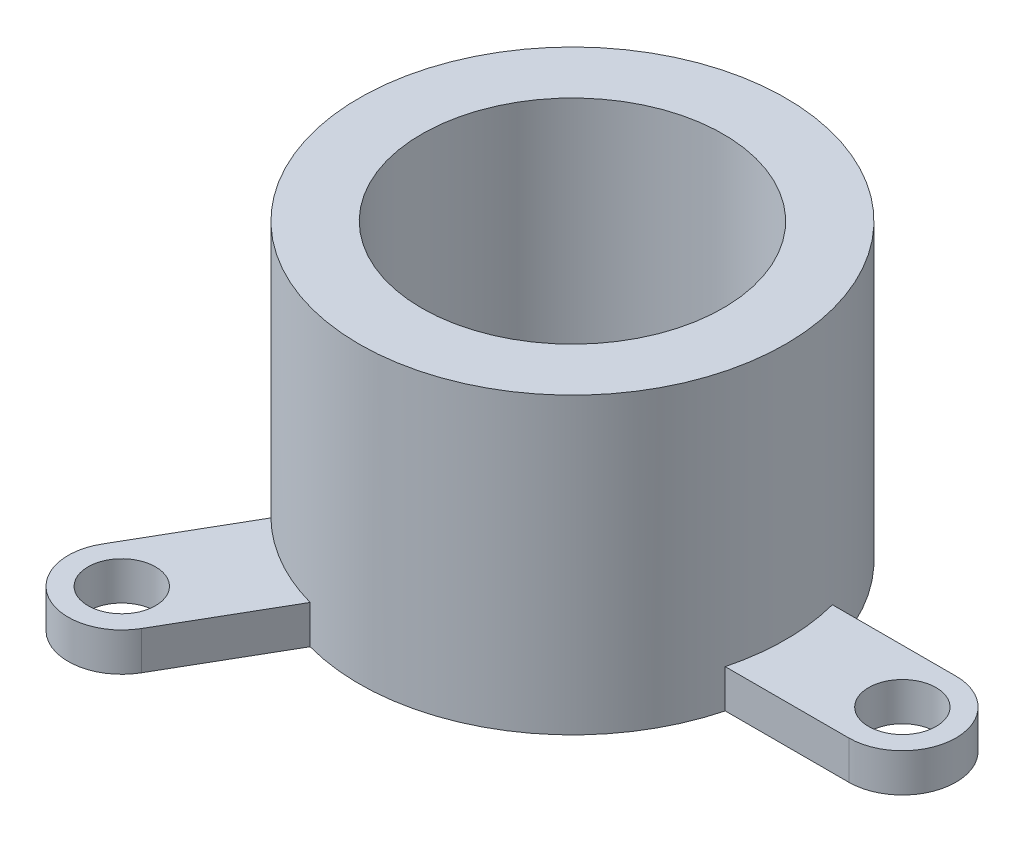
SolidWorks part; units mm, degrees
ref_plane "Front Plane" through (0, 0, 0) normal (0, 0, 1) x (1, 0, 0)
ref_plane "Top Plane" through (0, 0, 0) normal (0, 1, 0) x (1, 0, 0)
ref_plane "Right Plane" through (0, 0, 0) normal (1, 0, 0) x (0, 0, -1)
sketch "Sketch1" plane through (0, 0, 0) normal (0, 1, 0) x (1, 0, 0)
  circle A0 centre (0, 0) radius 35.3553
  circle A1 centre (0, 0) radius 50
extrude "Boss-Extrude1" add sketch "Sketch1" along normal blind 69
sketch "Sketch2" plane through (0, 0, 0) normal (0, -1, 0) x (1, 0, 0)
  line L0 (77.3632, 12.5646) -> (48.3956, 12.5646)
  line L4 (77.3632, -12.5646) -> (48.3956, -12.5646)
  arc A0 (48.3956, -12.5646) -> (48.3956, 12.5646) centre (0, 0) ccw
  arc A2 (77.3632, -12.5646) -> (77.3632, 12.5646) centre (77.3632, 0) ccw
  circle A3 centre (77.3632, 0) radius 7.9112
extrude "Boss-Extrude2" add sketch "Sketch2" against normal blind 9
ref_axis "Axis1" through (0, -3.45, 0) along (0, 1, 0)
pattern_circular "CirPattern1" count 3 over 360 about axis through (0, -3.45, 0) along (0, 1, 0) of "Boss-Extrude2"
